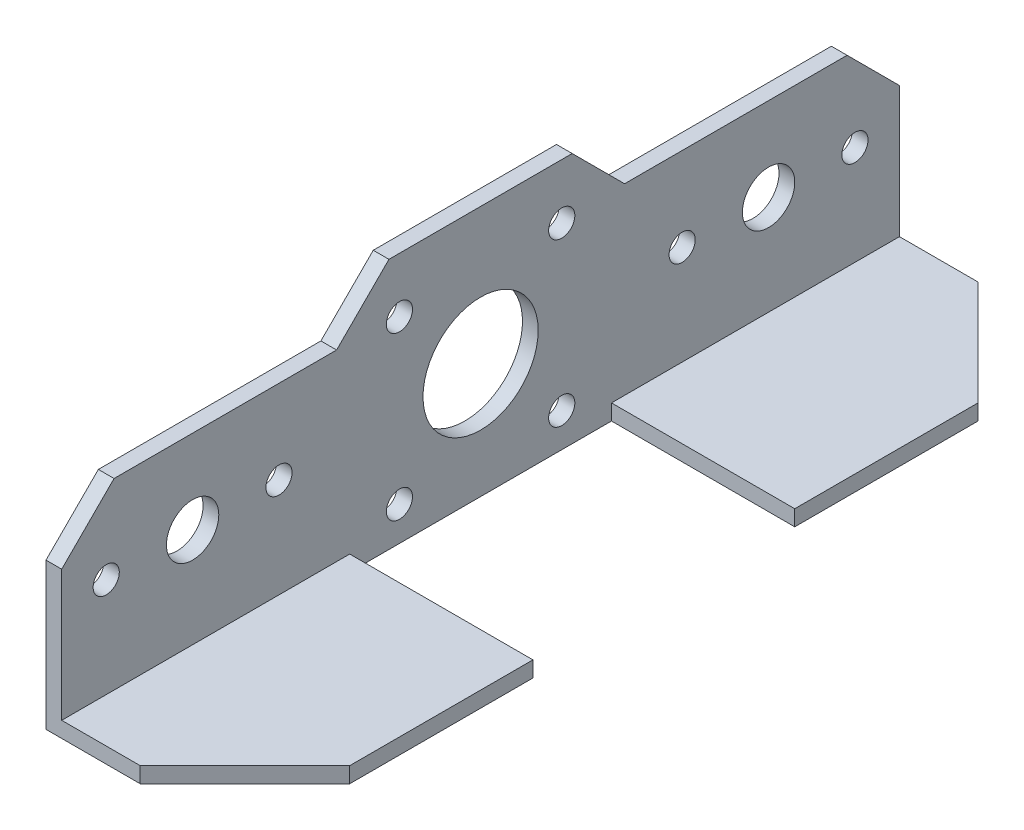
SolidWorks part; units mm, degrees
ref_plane "Alzado" through (0, 0, 0) normal (0, 0, 1) x (1, 0, 0)
ref_plane "Planta" through (0, 0, 0) normal (0, 1, 0) x (1, 0, 0)
ref_plane "Vista lateral" through (0, 0, 0) normal (1, 0, 0) x (0, 0, -1)
sketch "Croquis1" plane through (0, 0, 0) normal (0, 0, 1) x (1, 0, 0)
  line L0 (0, 0) -> (0, 38)
  line L1 (0, 0) -> (38, 0)
  line L2 (3, 3) -> (38, 3)
  line L3 (3, 3) -> (3, 38)
  line L4 (0, 38) -> (3, 38)
  line L5 (38, 3) -> (38, 0)
  dimension "D1" = 38
  dimension "D2" = 3
extrude "Saliente-Extruir1" add sketch "Croquis1" along normal blind 80 and the other way blind 80
sketch "Croquis2" plane through (0, 3, 0) normal (0, 1, 0) x (1, 0, 0)
  line L0 (3, 0) -> (38, 0) construction
  line L1 (3, 80) -> (3, -80) construction
  line L2 (38, 80) -> (38, -80) construction
  line L3 (3, 25) -> (3, -25)
  line L4 (3, -25) -> (38, -25)
  line L5 (38, -25) -> (38, 25)
  line L6 (3, 25) -> (38, 25)
  dimension "D1" = 25
extrude "Cortar-Extruir1" cut sketch "Croquis2" against normal up to surface (3 mm away) up to face at (19, 0, 0)
chamfer "Chaflán1" distance 20 angle 45 2 edges at (38, 1.5, -80) (38, 1.5, 80)
sketch "Croquis3" plane through (3, 0, 0) normal (1, 0, 0) x (0, 0, -1)
  line L0 (0, 0) -> (0, 38) construction
  line L1 (25, 0) -> (-25, 0) construction
  line L2 (80, 38) -> (-80, 38) construction
  line L3 (-80, 22) -> (0, 22) construction
  line L4 (-80, 3) -> (-80, 38) construction
  line L5 (-55, 38) -> (-55, 22) construction
  line L6 (-38.5, 22) -> (-71.5, 22) construction
  circle A0 centre (-55, 22) radius 5
  circle A1 centre (-71.5, 22) radius 2.5
  circle A2 centre (-38.5, 22) radius 2.5
  circle A3 centre (38.5, 22) radius 2.5
  circle A4 centre (55, 22) radius 5
  circle A5 centre (71.5, 22) radius 2.5
  point P16 (-55, 22)
  dimension "D4" = 10
  dimension "D5" = 5
  dimension "D1" = 16
  dimension "D2" = 55
  dimension "D3" = 33
extrude "Cortar-Extruir2" cut sketch "Croquis3" against normal up to surface (3 mm away) up to face at (0, 19, 0)
sketch "Croquis4" plane through (0, 0, 0) normal (-1, 0, 0) x (0, 0, 1)
  line L0 (0, 0) -> (0, 43) construction
  line L1 (-80, 0) -> (80, 0) construction
  line L2 (-80, 38) -> (80, 38) construction
  line L3 (-27.5, 48) -> (27.5, 48)
  line L4 (-27.5, 48) -> (-27.5, 38)
  line L5 (-27.5, 38) -> (27.5, 38)
  line L6 (27.5, 48) -> (27.5, 38)
  line L7 (-27.5, 48) -> (27.5, 38) construction
  line L8 (-27.5, 38) -> (27.5, 48) construction
  dimension "D1" = 10
  dimension "D2" = 55
extrude "Saliente-Extruir2" add sketch "Croquis4" against normal up to surface (3 mm away) up to face at (3, 22, -69)
sketch "Croquis5" plane through (0, 0, 0) normal (-1, 0, 0) x (0, 0, 1)
  line L0 (-55, 22) -> (55, 22) construction
  line L2 (-15.5, 6.5) -> (15.5, 6.5) construction
  line L3 (-15.5, 6.5) -> (-15.5, 37.5) construction
  line L4 (-15.5, 37.5) -> (15.5, 37.5) construction
  line L5 (15.5, 6.5) -> (15.5, 37.5) construction
  line L6 (-15.5, 6.5) -> (15.5, 37.5) construction
  line L7 (-15.5, 37.5) -> (15.5, 6.5) construction
  circle A0 centre (-15.5, 37.5) radius 2.5
  circle A1 centre (15.5, 37.5) radius 2.5
  circle A2 centre (15.5, 6.5) radius 2.5
  circle A3 centre (-15.5, 6.5) radius 2.5
  circle A4 centre (0, 22) radius 11
  point P4 (0, 22)
  dimension "D3" = 5
  dimension "D4" = 22
  dimension "D1" = 31
  dimension "D2" = 31
extrude "Cortar-Extruir3" cut sketch "Croquis5" against normal up to surface (3 mm away) up to face at (3, 22, -69)
chamfer "Chaflán2" distance 10 angle 45 4 edges at (1.5, 38, 80) (1.5, 38, -80) (1.5, 48, -27.5) (1.5, 48, 27.5)
